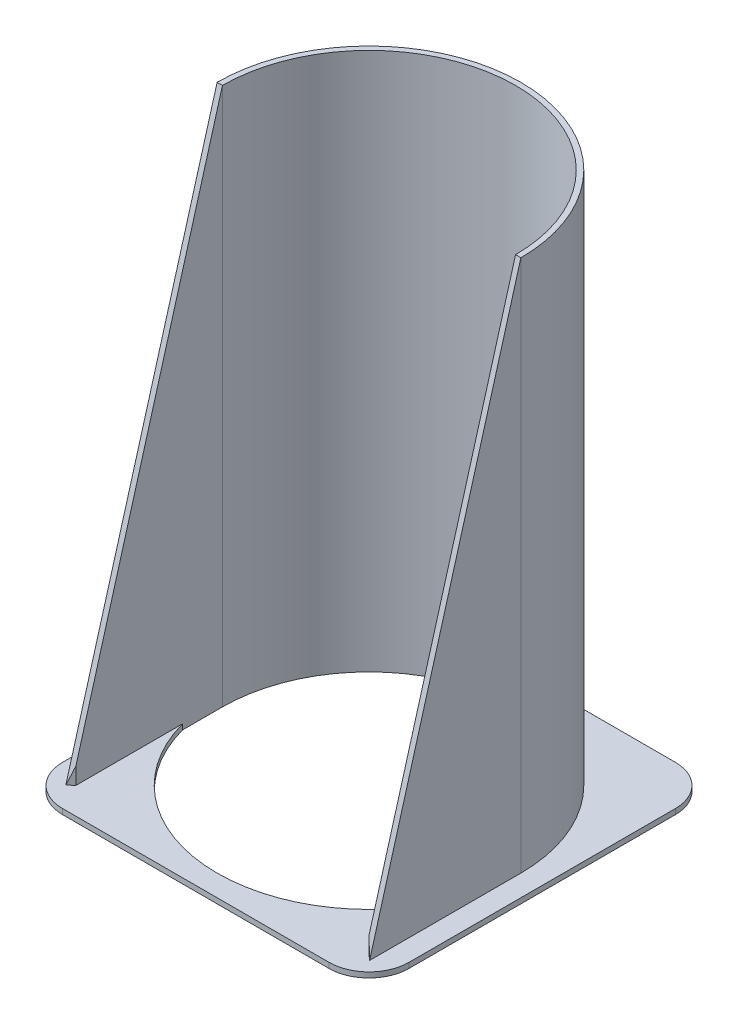
SolidWorks part; units mm, degrees
ref_plane "Plan de face" through (0, 0, 0) normal (0, 0, 1) x (1, 0, 0)
ref_plane "Plan de dessus" through (0, 0, 0) normal (0, 1, 0) x (1, 0, 0)
ref_plane "Plan de droite" through (0, 0, 0) normal (1, 0, 0) x (0, 0, -1)
sketch "Esquisse1" plane through (0, 0, 0) normal (0, 1, 0) x (1, 0, 0)
  line L0 (0, 0) -> (150, 150) construction
  line L1 (0, 0) -> (150, 0) construction
  line L2 (0, 0) -> (0, 150) construction
  line L3 (0, 150) -> (150, 150) construction
  line L4 (150, 0) -> (150, 150) construction
  line L5 (103.5, 46.3916) -> (46.5, 46.6084) construction
  line L6 (42.5, 42.5) -> (107.5, 42.5)
  line L7 (42.5, 42.5) -> (42.5, 107.5)
  line L8 (42.5, 107.5) -> (107.5, 107.5)
  line L9 (107.5, 42.5) -> (107.5, 107.5)
  line L10 (42.5, 42.5) -> (107.5, 107.5) construction
  line L11 (42.5, 107.5) -> (107.5, 42.5) construction
  line L12 (46.5, 75) -> (46.5, 46.6084)
  line L13 (47.5, 75) -> (47.5, 47.5)
  line L14 (103.5, 46.5) -> (103.5, 46.3916)
  line L17 (46.5, 46.6084) -> (47.5, 47.5)
  line L18 (75, 75) -> (75, 46.5) construction
  line L19 (103.5, 46.6084) -> (102.5, 47.5)
  line L20 (102.5, 75) -> (102.5, 47.5)
  line L21 (103.5, 75) -> (103.5, 46.6084)
  circle A0 centre (75, 75) radius 22.5 construction
  arc A1 (102.5, 75) -> (47.5, 75) centre (75, 75) ccw
  arc A2 (74.7833, 46.5008) -> (75, 46.5) centre (75, 75) ccw
  arc A3 (47.5, 75) -> (55.5546, 55.5546) centre (75, 75) ccw construction
  arc A4 (47.5, 67.5167) -> (54.8475, 54.8475) centre (75, 75) ccw
  arc A5 (55.5546, 55.5546) -> (94.4454, 55.5546) centre (75, 75) ccw construction
  arc A6 (54.8475, 54.8475) -> (74.7833, 46.5008) centre (75, 75) ccw
  arc A7 (75, 46.5) -> (95.1525, 54.8475) centre (75, 75) ccw
  arc A8 (103.5, 75) -> (46.5, 75) centre (75, 75) ccw
  arc A9 (95.1525, 54.8475) -> (102.5, 67.5167) centre (75, 75) ccw
  arc A10 (94.4454, 55.5546) -> (102.5, 75) centre (75, 75) ccw construction
  arc A11 (46.5, 75) -> (47.5, 67.5167) centre (75, 75) ccw construction
  arc A12 (102.5, 67.5167) -> (103.5, 75) centre (75, 75) ccw construction
  point P16 (75, 46.5)
  point P21 (74.7833, 46.5)
  dimension "D3" = 45
  dimension "D4" = 55
  dimension "D5" = 57
  dimension "D6" = 65
  dimension "D1" = 150
  dimension "D2" = 150
extrude "Boss.-Extru.1" add sketch "Esquisse1" along normal blind 1 contours L6 L9 L8 L7 A2 | A2 A1 region at (43.4192, 0, -75) region at (75, 0, -102.6947)
extrude "Boss.-Extru.2" add sketch "Esquisse1<3>" along normal blind 100 from surface contours A2 A1 region at (75, 0, -102.6947) starting at face at (75, 1, -72.8792)
sketch "Esquisse1<3>" plane through (0, 0, 0) normal (0, 1, 0) x (1, 0, 0) same geometry as "Esquisse1"
sketch "Esquisse2" plane through (46.5, 0, 0) normal (-1, 0, 0) x (0, 0, 1)
  line L0 (-75, 1) -> (-103.5, 1) construction
  line L4 (-75, 1) -> (-46.6084, 1)
  line L5 (-46.6084, 1) -> (-46.6084, 101)
  line L6 (-46.6084, 101) -> (-75, 101)
  line L7 (-75, 101) -> (-75, 1)
  line L8 (-75, 1) -> (-46.6084, 1)
  line L9 (-46.6084, 1) -> (-46.6084, 101)
  line L10 (-46.6084, 101) -> (-75, 101)
  line L11 (-75, 101) -> (-75, 1)
  line L16 (-75, 1) -> (-103.5, 1)
  line L17 (-103.5, 1) -> (-103.5, 101)
  line L18 (-75, 101) -> (-103.5, 101)
  line L19 (-46.6084, 1) -> (-75, 101)
  point P7 (-75.8275, 101)
  line M6 (-46.6084, 1) -> (-46.6084, 101)
  line M7 (-46.6084, 101) -> (-75, 101)
  dimension "D1" = 0
extrude "Enlèv. mat.-Extru.1" cut sketch "Esquisse2" against normal up to surface (57 mm away) contours L19 M6 M7 region at (46.5, 67.6667, -56.0722) up to face at (103.5, 51, -60.8042)
fillet "Congé1" radius 7.5 4 edges at (42.5, 0.5, -42.5) (42.5, 0.5, -107.5) (107.5, 0.5, -107.5) (107.5, 0.5, -42.5)
